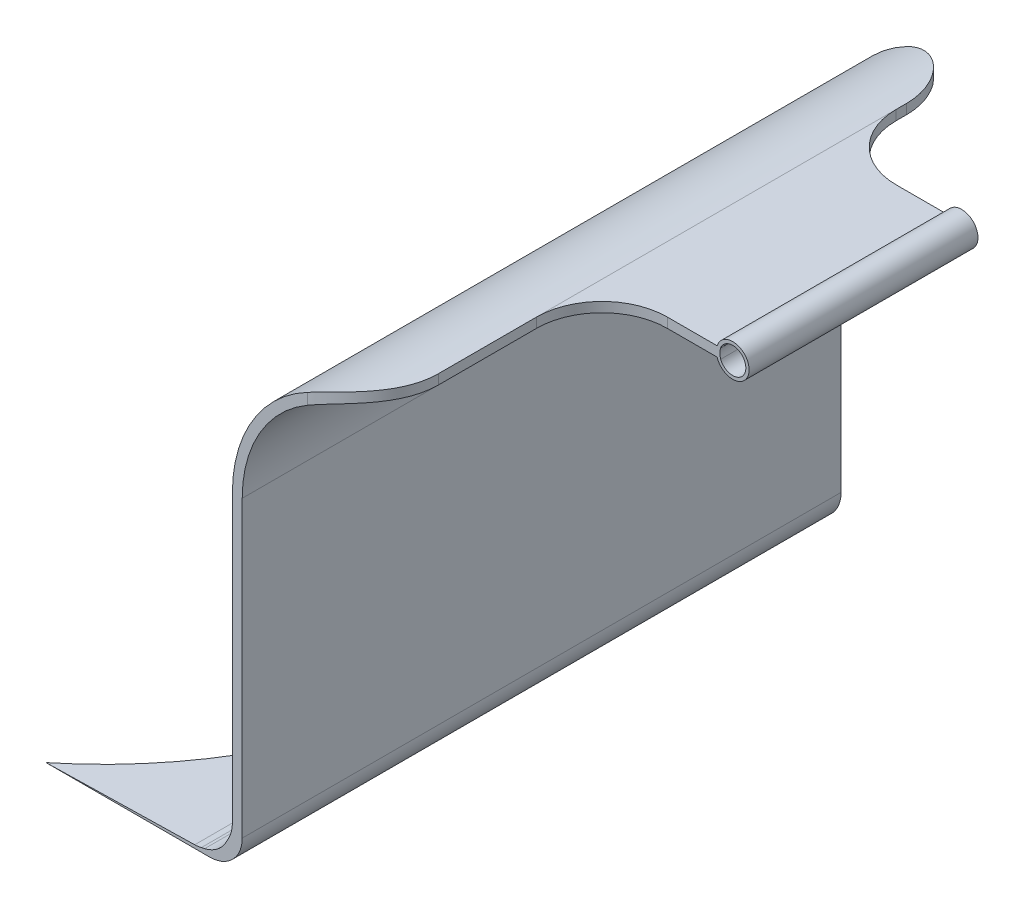
SolidWorks part; units mm, degrees
ref_plane "Front Plane" through (0, 0, 0) normal (0, 0, 1) x (1, 0, 0)
ref_plane "Top Plane" through (0, 0, 0) normal (0, 1, 0) x (1, 0, 0)
ref_plane "Right Plane" through (0, 0, 0) normal (1, 0, 0) x (0, 0, -1)
sketch "Sketch1" plane through (0, 0, 0) normal (0, 0, 1) x (1, 0, 0)
  line L0 (0, 71.8868) -> (-80, 71.8868) construction
  line L1 (-80, 71.8868) -> (-80, -68.1132) construction
  line L2 (-80, -68.1132) -> (-140, -68.1132) construction
  line L3 (0, 71.8868) -> (-40, 71.8868)
  line L4 (-80, 31.8868) -> (-80, -58.1132)
  line L5 (-90, -68.1132) -> (-140, -68.1132)
  line L6 (0, 74.8868) -> (-40, 74.8868)
  line L7 (-83, 31.8868) -> (-83, -55.577)
  line L8 (-83, 31.8868) -> (-83, -58.1132) construction
  line L9 (-140, -68.1132) -> (-94.515, -67.1226)
  line L10 (-92.4973, -66.8719) -> (-91.4768, -66.6378)
  line L11 (-84.9211, -61.6569) -> (-84.2088, -60.3429)
  line L12 (0, 74.8868) -> (0, 71.8868)
  line L13 (-90, -65.1132) -> (-140, -65.1132) construction
  arc A0 (-80, 31.8868) -> (-40, 71.8868) centre (-40, 31.8868) cw
  arc A1 (-80, -58.1132) -> (-90, -68.1132) centre (-90, -58.1132) cw
  arc A2 (-83, 31.8868) -> (-40, 74.8868) centre (-40, 31.8868) cw
  arc A3 (-83, -55.577) -> (-84.2088, -60.3429) centre (-93, -55.577) cw
  arc A4 (-83, -58.1132) -> (-90, -65.1132) centre (-90, -58.1132) cw construction
  arc A5 (-94.515, -67.1226) -> (-92.4973, -66.8719) centre (-94.7328, -57.125) ccw
  arc A6 (-91.4768, -66.6378) -> (-84.9211, -61.6569) centre (-93.7123, -56.8909) ccw
  dimension "D4" = 40
  dimension "D5" = 10
  dimension "D7" = 10
  dimension "D1" = 80
  dimension "D2" = 140
  dimension "D3" = 60
  dimension "D6" = 3
extrude "Boss-Extrude2" add sketch "Sketch1" along normal mid plane 210
sketch "Sketch2" plane through (0, 74.8868, 0) normal (0, 1, 0) x (1, 0, 0)
  line L0 (0, -105) -> (0, 105) construction
  line L1 (-40, 105) -> (0, 105)
  line L2 (-40, 105) -> (-40, 35)
  line L3 (-40, 35) -> (0, 35)
  line L4 (0, 105) -> (0, 35)
  line L5 (-40, -105) -> (-40, 105) construction
  line L6 (0, -105) -> (-40, -105)
  line L7 (0, -105) -> (0, -35)
  line L8 (0, -35) -> (-40, -35)
  line L9 (-40, -105) -> (-40, -35)
  dimension "D1" = 70
  dimension "D2" = 70
extrude "Cut-Extrude1" cut sketch "Sketch2" against normal mid plane 210
fillet "Fillet1" radius 20 2 edges at (-40, 73.3868, -35) (-40, 73.3868, 35)
fillet "Fillet2" radius 20 2 edges at (-40, 73.3868, 105) (-40, 73.3868, -105)
sketch "Sketch3" plane through (0, 0, 35) normal (0, 0, 1) x (1, 0, 0)
  line L0 (0, 71.8868) -> (0, 74.8868) construction
  circle A0 centre (0, 73.3868) radius 5
  circle A1 centre (0, 73.3868) radius 4
  dimension "D1" = 10
  dimension "D2" = 1
extrude "Boss-Extrude3" add sketch "Sketch3" against normal blind 70
sketch "Sketch4" plane through (0, 0, 35) normal (0, 0, 1) x (1, 0, 0)
  line L0 (0, 71.8868) -> (0, 74.8868) construction
  circle A0 centre (0, 73.3868) radius 3.9607
extrude "Cut-Extrude2" cut sketch "Sketch4" against normal blind 70
sketch "Sketch5" plane through (0, 74.8868, 0) normal (0, 1, 0) x (1, 0, 0)
  line L0 (-40, 55) -> (-40, 85) construction
  line L1 (-40, 78.129) -> (-149.6672, 78.129)
  line L2 (-40, 78.129) -> (-40, 109.3411)
  line L3 (-40, 109.3411) -> (-149.6672, 109.3411)
  line L4 (-149.6672, 78.129) -> (-149.6672, 109.3411)
extrude "Cut-Extrude3" cut sketch "Sketch5" against normal through all
fillet "Fillet3" radius 20 1 edges at (-40, 73.3868, -78.129)
sketch "Sketch6" plane through (1.4164, -65.0333, 0) normal (-0.0218, 0.9998, 0) x (0.9998, 0.0218, 0)
  line L3 (-141.4499, 78.129) -> (-141.4499, -105)
  arc A0 (-141.4499, -105) -> (-141.4499, 78.129) centre (-211.7007, -13.4355) ccw
extrude "Cut-Extrude4" cut sketch "Sketch6" against normal through all
